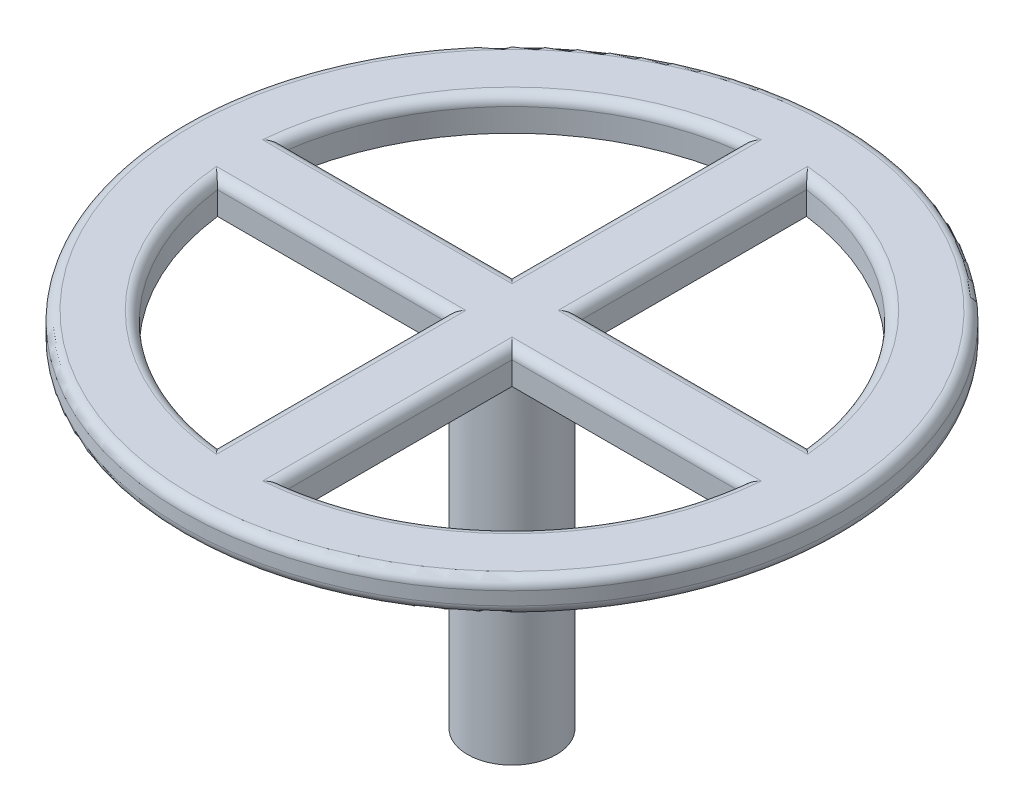
SolidWorks part; units mm, degrees
ref_plane "Front Plane" through (0, 0, 0) normal (0, 0, 1) x (1, 0, 0)
ref_plane "Top Plane" through (0, 0, 0) normal (0, 1, 0) x (1, 0, 0)
ref_plane "Right Plane" through (0, 0, 0) normal (1, 0, 0) x (0, 0, -1)
sketch "Sketch2" plane through (0, 0, 0) normal (0, 1, 0) x (1, 0, 0)
  circle A0 centre (0, 0) radius 100
extrude "Boss-Extrude1" add sketch "Sketch2" along normal blind 5 and the other way blind 5
sketch "Sketch3" plane through (0, 5, 0) normal (0, 1, 0) x (1, 0, 0)
  circle A0 centre (0, 0) radius 80
extrude "Cut-Extrude1" cut sketch "Sketch3" against normal through all
sketch "Sketch4" plane through (0, 0, 0) normal (0, 1, 0) x (1, 0, 0)
  line L1 (80, -10) -> (-80, -10)
  line L2 (80, -10) -> (80, 10)
  line L3 (80, 10) -> (-80, 10)
  line L4 (-80, -10) -> (-80, 10)
  dimension "D1" = 80
  dimension "D2" = 80
  dimension "D3" = 10
  dimension "D4" = 10
extrude "Boss-Extrude2" add sketch "Sketch4" along normal mid plane 10
sketch "Sketch5" plane through (0, 0, 0) normal (0, 1, 0) x (1, 0, 0)
  line L1 (-10, 80) -> (10, 80)
  line L2 (-10, 80) -> (-10, -80)
  line L3 (-10, -80) -> (10, -80)
  line L4 (10, 80) -> (10, -80)
  dimension "D1" = 80
  dimension "D2" = 80
  dimension "D3" = 10
  dimension "D4" = 10
extrude "Boss-Extrude3" add sketch "Sketch5" along normal mid plane 10
sketch "Sketch7" plane through (0, -5, 0) normal (0, -1, 0) x (1, 0, 0)
  circle A0 centre (0, 0) radius 13.5
extrude "Boss-Extrude4" add sketch "Sketch7" along normal blind 100
fillet "Fillet1" radius 3 13 edges at (0, 5, 100) (-56.5685, 5, -56.5685) (-44.6863, 5, -10) (-10, 5, -44.6863) (44.6863, 5, 10) (10, 5, 44.6863) (56.5685, 5, 56.5685) (-44.6863, 5, 10) (-56.5685, 5, 56.5685) (-10, 5, 44.6863) (44.6863, 5, -10) (56.5685, 5, -56.5685) (10, 5, -44.6863)
fillet "Fillet3" radius 3 1 edges at (0, -5, 100)
